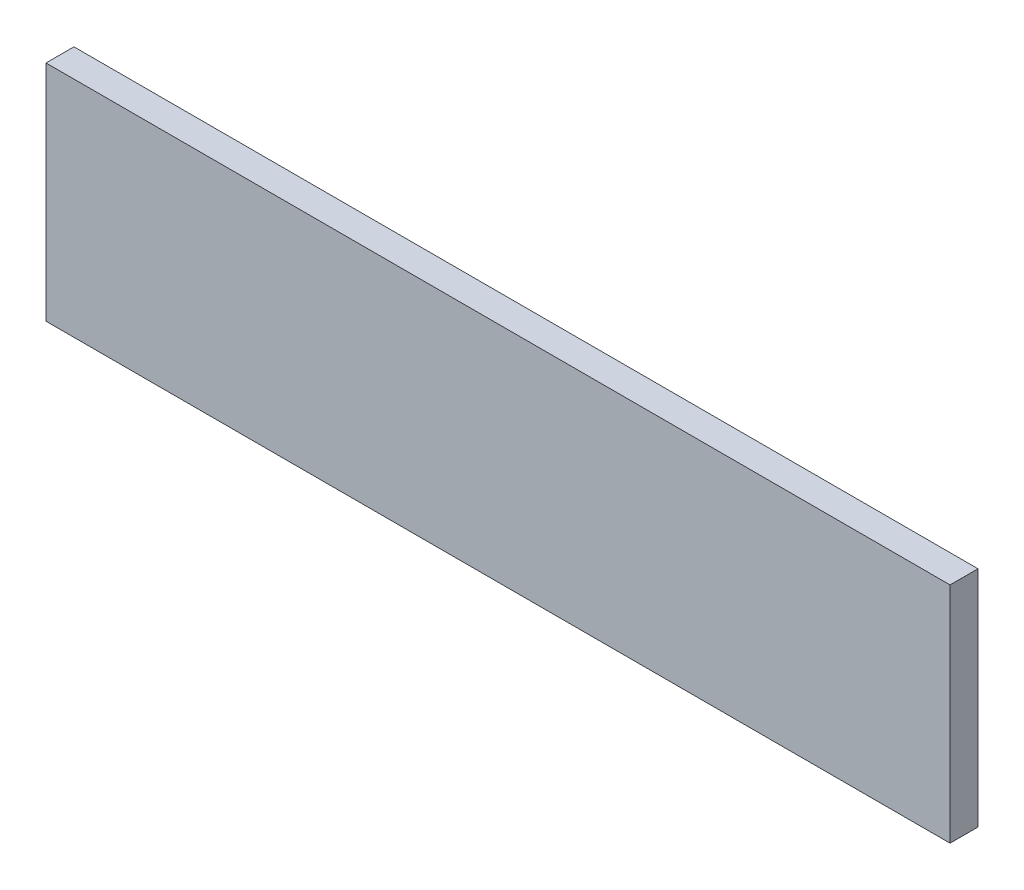
SolidWorks part; units mm, degrees
material "Acrylic (Medium-high impact)"
ref_plane "Front Plane" through (0, 0, 0) normal (0, 0, 1) x (1, 0, 0)
ref_plane "Top Plane" through (0, 0, 0) normal (0, 1, 0) x (1, 0, 0)
ref_plane "Right Plane" through (0, 0, 0) normal (1, 0, 0) x (0, 0, -1)
sketch "Sketch1" plane through (0, 0, 0) normal (0, 0, 1) x (1, 0, 0)
  line L1 (48.5, -12) -> (-48.5, -12)
  line L2 (48.5, -12) -> (48.5, 12)
  line L3 (48.5, 12) -> (-48.5, 12)
  line L4 (-48.5, -12) -> (-48.5, 12)
  line L5 (48.5, -12) -> (-48.5, 12) construction
  line L6 (48.5, 12) -> (-48.5, -12) construction
  point P0 (0, 0)
  dimension "D1" = 97
  dimension "D2" = 24
extrude "Boss-Extrude1" add sketch "Sketch1" along normal blind 3
